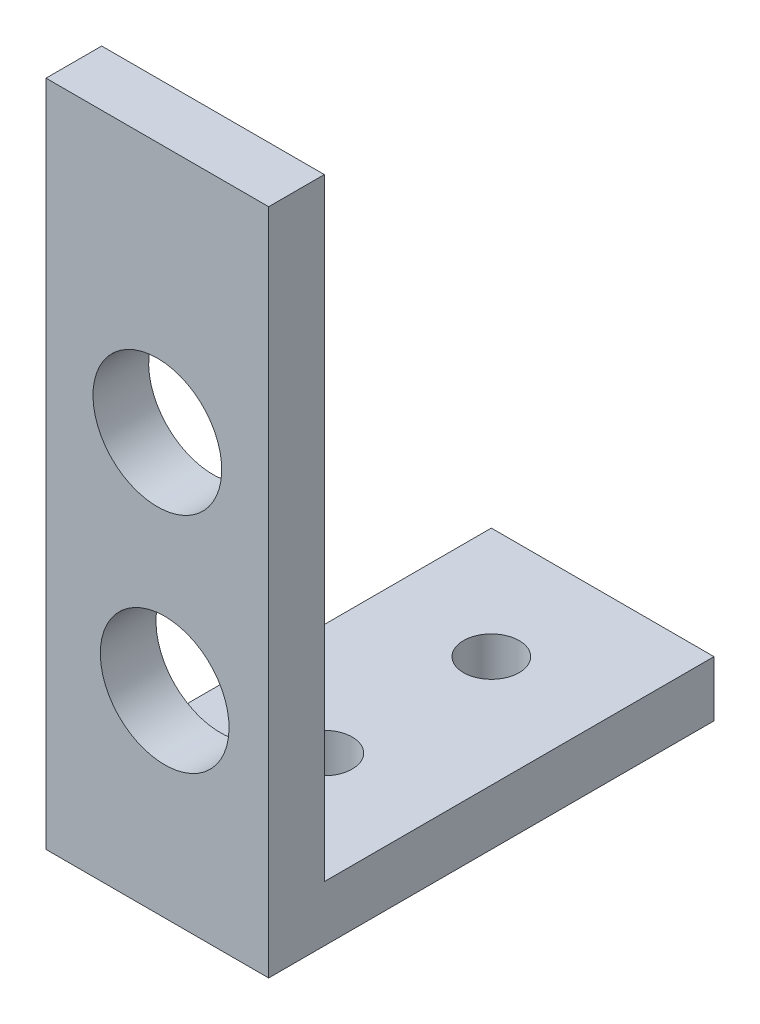
SolidWorks part; units mm, degrees
ref_plane "Front Plane" through (0, 0, 0) normal (0, 0, 1) x (1, 0, 0)
ref_plane "Top Plane" through (0, 0, 0) normal (0, 1, 0) x (1, 0, 0)
ref_plane "Right Plane" through (0, 0, 0) normal (1, 0, 0) x (0, 0, -1)
sketch "Sketch1" plane through (0, 0, 0) normal (1, 0, 0) x (0, 0, -1)
  line L0 (0, 76.2) -> (0, 0)
  line L1 (0, 0) -> (50.8, 0)
  line L2 (6.35, 76.2) -> (6.35, 6.35)
  line L3 (6.35, 6.35) -> (50.8, 6.35)
  line L4 (0, 76.2) -> (6.35, 76.2)
  line L5 (50.8, 6.35) -> (50.8, 0)
  dimension "D1" = 76.2
  dimension "D2" = 50.8
  dimension "D3" = 6.35
extrude "Boss-Extrude1" add sketch "Sketch1" along normal blind 25.4
sketch "Sketch2" plane through (0, 6.35, 0) normal (0, 1, 0) x (1, 0, 0)
  line L1 (25.4, 6.35) -> (0, 6.35) construction
  circle A0 centre (12.7, 38.1) radius 3.175
  circle A1 centre (12.7, 19.05) radius 3.175
  dimension "D1" = 12.7
  dimension "D2" = 31.75
  dimension "D3" = 6.35
extrude "Cut-Extrude1" cut sketch "Sketch2" against normal up to next
hole_wizard "5/8-18 Tapped Hole1" positions "Sketch4" profile "Sketch3" tap size "5/8-18" standard "ANSI Inch" end condition up to next
sketch "Sketch4" plane through (0, 0, -6.35) normal (0, 0, -1) x (-1, 0, 0)
  line L0 (-25.4, 0) -> (0, 0) construction
  line L1 (-25.4, 6.35) -> (-25.4, 76.2) construction
  point P0 (-12.7, 47.5488)
  point P2 (-13.5367, 22.4695)
  dimension "D1" = 47.5488
  dimension "D2" = 12.7
sketch "Sketch3" plane through (12.7, 47.5488, -6.35) normal (1, 0, 0) x (0, 1, 0)
  line L0 (0, 0) -> (0, 6.35)
  line L1 (0, 6.35) -> (7.3419, 6.35)
  line L2 (7.3419, 6.35) -> (7.3419, 0)
  line L5 (7.3419, 0) -> (0, 0)
  line L11 (0, -6.35) -> (0, 107.95) construction
  dimension "Thread Major Dia." = 14.6837
  dimension "Thru Tap Drill Depth" = 6.35
